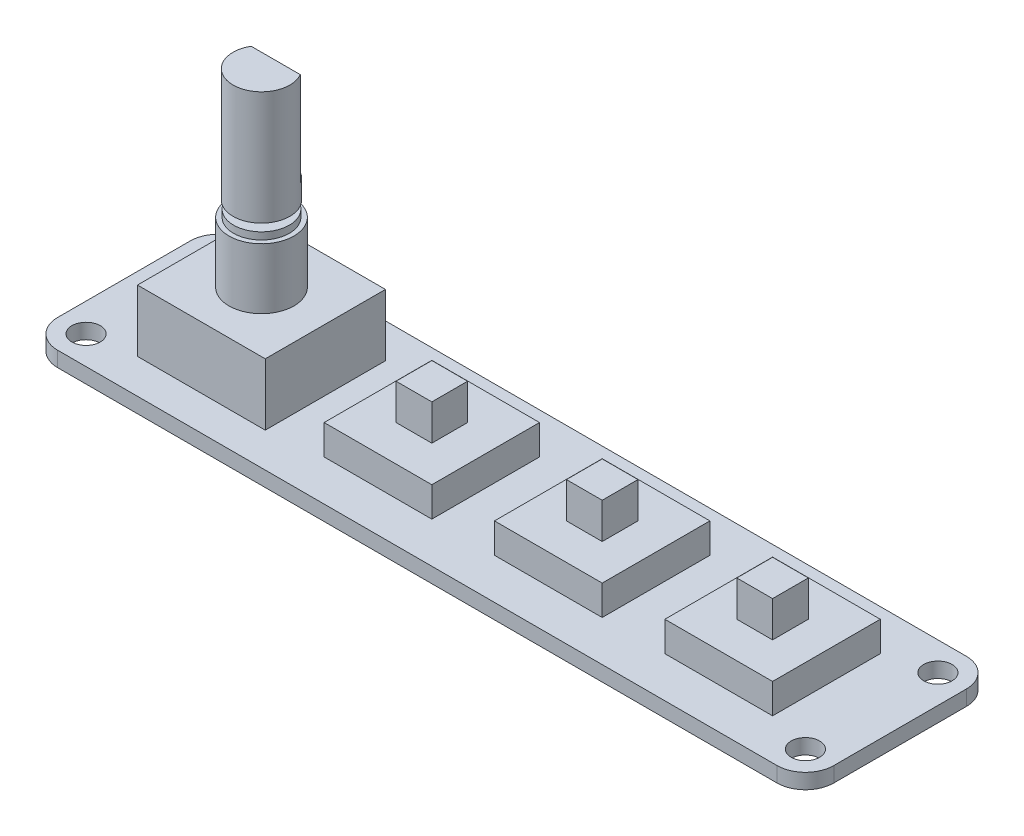
SolidWorks part; units mm, degrees
ref_plane "Front Plane" through (0, 0, 0) normal (0, 0, 1) x (1, 0, 0)
ref_plane "Top Plane" through (0, 0, 0) normal (0, 1, 0) x (1, 0, 0)
ref_plane "Right Plane" through (0, 0, 0) normal (1, 0, 0) x (0, 0, -1)
sketch "Sketch1" plane through (0, 0, 0) normal (0, 1, 0) x (1, 0, 0)
  line L1 (41, 10) -> (-41, 10)
  line L2 (41, 10) -> (41, -10)
  line L3 (41, -10) -> (-41, -10)
  line L4 (-41, 10) -> (-41, -10)
  line L5 (41, 10) -> (-41, -10) construction
  line L6 (41, -10) -> (-41, 10) construction
  point P1 (0, 0)
  dimension "D1" = 20
  dimension "D2" = 82
extrude "Boss-Extrude1" add sketch "Sketch1" along normal blind 1.6
sketch "Sketch2" plane through (0, 1.6, 0) normal (0, 1, 0) x (1, 0, 0)
  line L1 (33.22, 5.69) -> (21.84, 5.69)
  line L2 (33.22, 5.69) -> (33.22, -5.69)
  line L3 (33.22, -5.69) -> (21.84, -5.69)
  line L4 (21.84, 5.69) -> (21.84, -5.69)
  line L5 (33.22, 5.69) -> (21.84, -5.69) construction
  line L6 (33.22, -5.69) -> (21.84, 5.69) construction
  line L7 (15.22, 5.69) -> (3.84, 5.69)
  line L8 (15.22, 5.69) -> (15.22, -5.69)
  line L9 (15.22, -5.69) -> (3.84, -5.69)
  line L10 (3.84, 5.69) -> (3.84, -5.69)
  line L11 (15.22, 5.69) -> (3.84, -5.69) construction
  line L12 (15.22, -5.69) -> (3.84, 5.69) construction
  line L13 (-2.78, 5.69) -> (-14.16, 5.69)
  line L14 (-2.78, 5.69) -> (-2.78, -5.69)
  line L15 (-2.78, -5.69) -> (-14.16, -5.69)
  line L16 (-14.16, 5.69) -> (-14.16, -5.69)
  line L17 (-2.78, 5.69) -> (-14.16, -5.69) construction
  line L18 (-2.78, -5.69) -> (-14.16, 5.69) construction
  line L19 (-33.22, 0) -> (33.22, 0) construction
  line L20 (-33.22, 6.35) -> (-19.72, 6.35)
  line L21 (-33.22, 6.35) -> (-33.22, -6.35)
  line L22 (-33.22, -6.35) -> (-19.72, -6.35)
  line L23 (-19.72, 6.35) -> (-19.72, -6.35)
  line L24 (-33.22, 6.35) -> (-19.72, -6.35) construction
  line L25 (-33.22, -6.35) -> (-19.72, 6.35) construction
  point P0 (27.53, 0)
  point P5 (9.53, 0)
  point P10 (-8.47, 0)
  point P17 (0, 0)
  point P19 (-26.47, 0)
  dimension "D1" = 18
  dimension "D2" = 18
  dimension "D3" = 11.38
  dimension "D5" = 13.5
  dimension "D6" = 12.7
  dimension "D7" = 18
extrude "Boss-Extrude2" add sketch "Sketch2" along normal blind 3.15 contours L13 L16 L15 L14 | L7 L10 L9 L8 | L1 L4 L3 L2 region at (27.53, 1.6, 0) region at (9.53, 1.6, 0) region at (-8.47, 1.6, 0)
extrude "Boss-Extrude3" add sketch "Sketch2<3>" along normal blind 6.53 contours L23 L20 L21 L22 region at (-26.47, 1.6, 0)
sketch "Sketch2<3>" plane through (0, 1.6, 0) normal (0, 1, 0) x (1, 0, 0) same geometry as "Sketch2"
sketch "Sketch3" plane through (0, 4.75, 0) normal (0, 1, 0) x (1, 0, 0)
  line L0 (-8.47, 5.69) -> (-8.47, 0) construction
  line L1 (-10.36, 1.89) -> (-6.58, 1.89)
  line L2 (-10.36, 1.89) -> (-10.36, -1.89)
  line L3 (-10.36, -1.89) -> (-6.58, -1.89)
  line L4 (-6.58, 1.89) -> (-6.58, -1.89)
  line L5 (-10.36, 1.89) -> (-6.58, -1.89) construction
  line L6 (-10.36, -1.89) -> (-6.58, 1.89) construction
  line L7 (7.64, 1.89) -> (11.42, 1.89)
  line L8 (7.64, 1.89) -> (7.64, -1.89)
  line L9 (7.64, -1.89) -> (11.42, -1.89)
  line L10 (11.42, 1.89) -> (11.42, -1.89)
  line L11 (7.64, 1.89) -> (11.42, -1.89) construction
  line L12 (7.64, -1.89) -> (11.42, 1.89) construction
  line L13 (29.42, 1.89) -> (25.64, 1.89)
  line L14 (29.42, 1.89) -> (29.42, -1.89)
  line L15 (29.42, -1.89) -> (25.64, -1.89)
  line L16 (25.64, 1.89) -> (25.64, -1.89)
  line L17 (29.42, 1.89) -> (25.64, -1.89) construction
  line L18 (29.42, -1.89) -> (25.64, 1.89) construction
  line L19 (-2.78, 5.69) -> (-14.16, 5.69) construction
  line L20 (9.53, 5.69) -> (9.53, 0) construction
  line L21 (15.22, 5.69) -> (3.84, 5.69) construction
  line L22 (27.53, 5.69) -> (27.53, 0) construction
  line L23 (33.22, 5.69) -> (21.84, 5.69) construction
  line L24 (33.22, 0) -> (-14.16, 0) construction
  line L25 (33.22, 5.69) -> (33.22, -5.69) construction
  line L26 (-14.16, 5.69) -> (-14.16, -5.69) construction
  point P0 (-8.47, 0)
  point P5 (9.53, 0)
  point P10 (27.53, 0)
  dimension "D1" = 3.78
extrude "Boss-Extrude4" add sketch "Sketch3" along normal blind 3.78
sketch "Sketch4" plane through (0, 0, 0) normal (0, 0, 1) x (1, 0, 0)
  line L0 (-26.47, 8.13) -> (-26.47, 26.7203) construction
  line L1 (-33.22, 8.13) -> (-19.72, 8.13) construction
  line L2 (-23.04, 8.13) -> (-23.04, 14.53)
  line L3 (-23.04, 14.53) -> (-23.525, 14.53)
  line L4 (-23.525, 14.53) -> (-23.525, 15.28)
  line L5 (-23.525, 15.28) -> (-24.885, 15.28)
  line L6 (-24.885, 15.28) -> (-24.885, 16.11)
  line L7 (-24.885, 16.11) -> (-23.47, 16.11)
  line L8 (-23.47, 16.11) -> (-23.47, 28.13)
  line L9 (-23.47, 28.13) -> (-26.47, 28.13)
  line L10 (-26.47, 28.13) -> (-26.47, 8.13)
  line L11 (-26.47, 8.13) -> (-23.04, 8.13)
  dimension "D1" = 6.86
  dimension "D2" = 5.89
  dimension "D3" = 3.17
  dimension "D4" = 6
  dimension "D5" = 6.4
  dimension "D6" = 0.75
  dimension "D7" = 0.83
  dimension "D8" = 20
revolve "Revolve1" add sketch "Sketch4" angle 360 about L0
sketch "Sketch5" plane through (0, 28.13, 0) normal (0, 1, 0) x (1, 0, 0)
  line L0 (-26.47, -2.945) -> (-26.47, 1.505) construction
  line L1 (-23.8748, 1.505) -> (-29.0652, 1.505)
  line L2 (-23.8748, 1.505) -> (-23.8748, 3)
  line L3 (-23.8748, 3) -> (-29.0652, 3)
  line L4 (-29.0652, 1.505) -> (-29.0652, 3)
  circle A0 centre (-26.47, 0) radius 2.945 construction
  circle A1 centre (-26.47, 0) radius 3 construction
  dimension "D1" = 4.45
extrude "Cut-Extrude1" cut sketch "Sketch5" against normal blind 10
sketch "Sketch6" plane through (0, 1.6, 0) normal (0, 1, 0) x (1, 0, 0)
  line L0 (0, 0) -> (0, 10) construction
  line L1 (41, 10) -> (-41, 10) construction
  line L2 (0, 0) -> (-41, 0) construction
  line L3 (-41, 10) -> (-41, -10) construction
  line L4 (-41, -10) -> (41, -10) construction
  circle A0 centre (-38, 7) radius 1.5
  circle A1 centre (-38, -7) radius 1.5
  circle A2 centre (38, -7) radius 1.5
  circle A3 centre (38, 7) radius 1.5
  dimension "D1" = 3
  dimension "D2" = 3
  dimension "D3" = 3
extrude "Cut-Extrude2" cut sketch "Sketch6" against normal through all
fillet "Fillet1" radius 3 4 edges at (41, 0.8, 10) (41, 0.8, -10) (-41, 0.8, 10) (-41, 0.8, -10)
